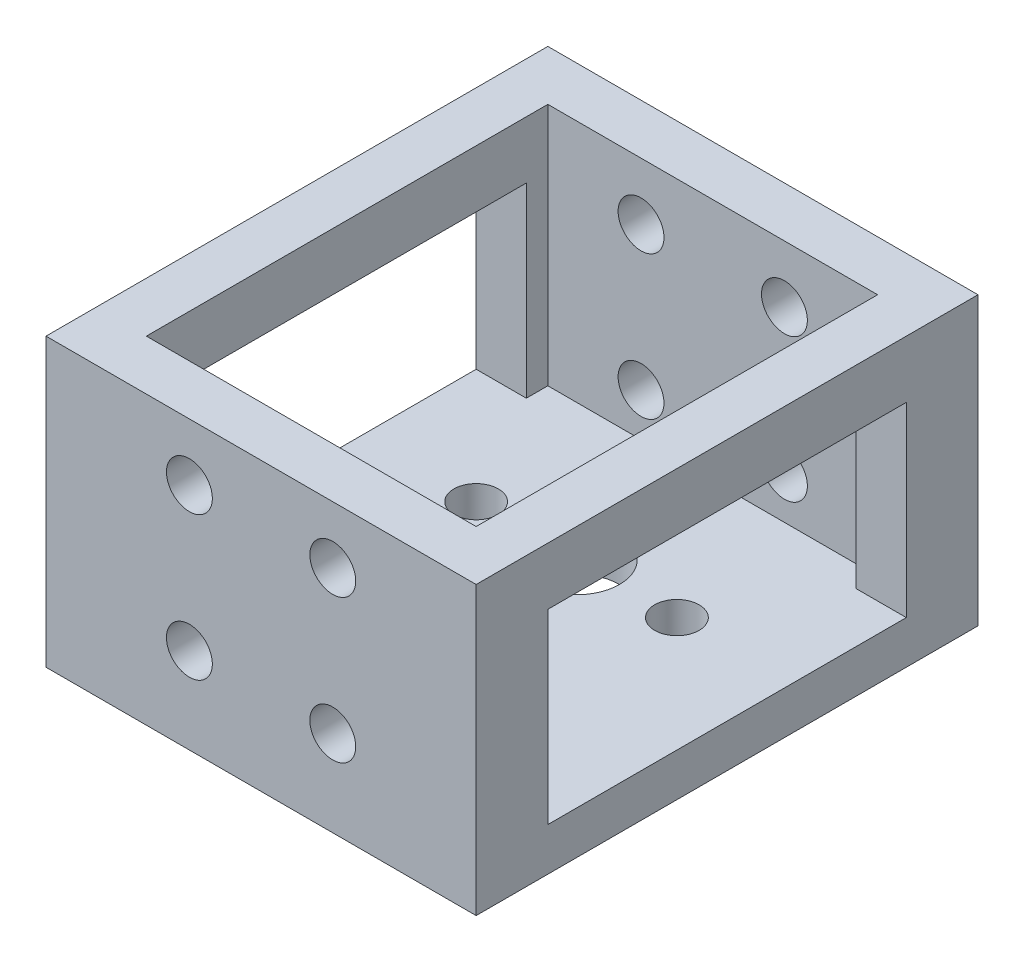
SolidWorks part; units mm, degrees
ref_plane "前视基准面" through (0, 0, 0) normal (0, 0, 1) x (1, 0, 0)
ref_plane "上视基准面" through (0, 0, 0) normal (0, 1, 0) x (1, 0, 0)
ref_plane "右视基准面" through (0, 0, 0) normal (1, 0, 0) x (0, 0, -1)
sketch "草图1" plane through (0, 0, 0) normal (0, 1, 0) x (1, 0, 0)
  line L0 (0, 0) -> (0, 14) construction
  line L1 (0, 0) -> (0, -14) construction
  line L2 (0, 0) -> (11.5, 0) construction
  line L3 (0, 0) -> (-11.5, 0) construction
  line L4 (0, 14) -> (11.5, 14)
  line L5 (11.5, 14) -> (11.5, 0)
  line L6 (11.5, -14) -> (0, -14)
  line L7 (-11.5, -14) -> (-11.5, 0)
  line L8 (-11.5, 14) -> (0, 14)
  line L9 (-11.5, 0) -> (-11.5, 14)
  line L10 (-11.5, -14) -> (0, -14)
  line L11 (11.5, -14) -> (11.5, 0)
  line L12 (-11.5, -14) -> (-11.5, -17.5)
  line L13 (11.5, -14) -> (11.5, -17.5)
  line L14 (-11.5, 17.5) -> (-11.5, 14)
  line L15 (11.5, 14) -> (11.5, 17.5)
  line L19 (-11.5, 17.5) -> (11.5, 17.5)
  line L22 (11.5, -17.5) -> (-11.5, -17.5)
  line L28 (-11.5, -14) -> (-8.5, -14)
  line L30 (11.5, 17.5) -> (15, 17.5)
  line L32 (15, 17.5) -> (15, -17.5)
  line L33 (11.5, -17.5) -> (15, -17.5)
  line L34 (-11.5, -17.5) -> (-15, -17.5)
  line L35 (-15, -17.5) -> (-15, 17.5)
  line L36 (-15, 17.5) -> (-11.5, 17.5)
extrude "凸台-拉伸2" add sketch "草图1" along normal blind 3 contours L6 L11 L5 L4 L8 L9 L7 L10 | L8 L4 | L6 L10 region at (0, 0, -15.75) region at (0, 0, 0) region at (0, 0, 15.75)
extrude "凸台-拉伸3" add sketch "草图1<4>" along normal blind 18 separate body contours L22 | L19 region at (0, 0, -15.75) region at (0, 0, 15.75)
sketch "草图1<4>" plane through (0, 0, 0) normal (0, 1, 0) x (1, 0, 0) same geometry as "草图1"
extrude "凸台-拉伸4" add sketch "草图1<5>" along normal blind 20 contours L36 L35 L34 L7 L9 | L33 L32 L30 L5 L11 | L10 | L6 | L4 | L8 region at (0, 0, -15.75) region at (13.25, 0, 0) region at (-13.25, 0, 0) region at (0, 0, 15.75)
sketch "草图1<5>" plane through (0, 0, 0) normal (0, 1, 0) x (1, 0, 0) same geometry as "草图1"
sketch "草图8" plane through (-15, 0, 0) normal (-1, 0, 0) x (0, 0, 1)
  line L0 (12.5, 10) -> (12.5, 3)
  line L1 (0, 3) -> (12.5, 3)
  line L2 (12.5, 10) -> (12.5, 16)
  line L3 (-12.5, 3) -> (0, 3)
  line L10 (-12.5, 3) -> (-12.5, 16)
  line L11 (-12.5, 16) -> (12.5, 16)
  point P2 (0, 0)
extrude "切除-拉伸5" cut sketch "草图8" against normal through all contours L11 L10 L2 region at (-15, 9.5, 0)
sketch "草图9" plane through (0, 0, 0) normal (0, -1, 0) x (1, 0, 0)
  line L0 (15, 17.5) -> (0, 17.5) construction
  line L1 (15, 17.5) -> (-15, 17.5) construction
  line L2 (0, 17.5) -> (0, 2.5) construction
  line L3 (0, 2.5) -> (0, -11.5) construction
  line L4 (0, -4.5) -> (-7, -4.5) construction
  line L5 (0, -4.5) -> (7, -4.5) construction
  circle A0 centre (0, -11.5) radius 1.55
  circle A1 centre (0, 2.5) radius 1.55
  circle A2 centre (7, -4.5) radius 1.55
  circle A3 centre (-7, -4.5) radius 1.55
  circle A4 centre (0, -4.5) radius 3
extrude "切除-拉伸6" cut sketch "草图9" against normal through all
sketch "草图10" plane through (0, 0, -17.5) normal (0, 0, -1) x (-1, 0, 0)
  line L0 (0, 0) -> (0, 6) construction
  line L2 (15, 0) -> (-15, 0) construction
  line L3 (0, 6) -> (-5, 6) construction
  line L4 (-5, 6) -> (-5, 16) construction
  line L5 (-5, 16) -> (5, 16) construction
  line L6 (5, 16) -> (5, 6) construction
  circle A0 centre (5, 6) radius 1.6
  circle A1 centre (-5, 6) radius 1.6
  circle A2 centre (-5, 16) radius 1.6
  circle A3 centre (5, 16) radius 1.6
extrude "切除-拉伸7" cut sketch "草图10" against normal through all
